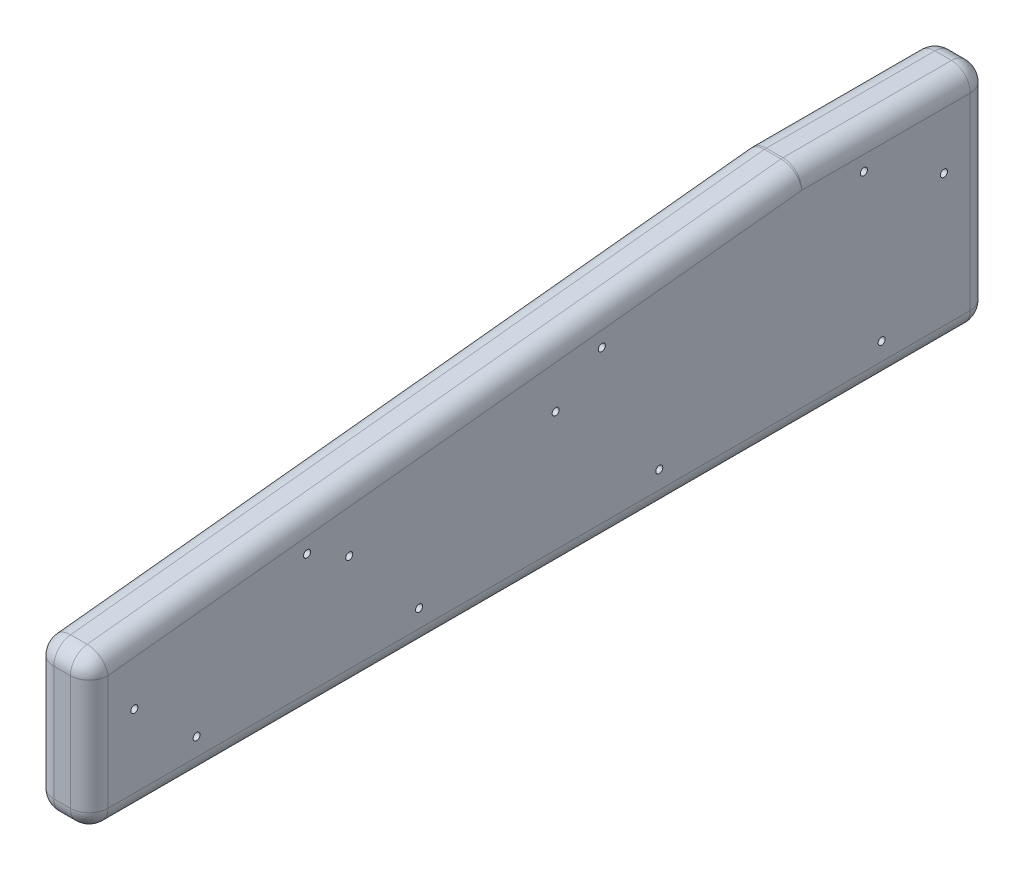
SolidWorks part; units mm, degrees
material "Mahogany"
ref_plane "Front Plane" through (0, 0, 0) normal (0, 0, 1) x (1, 0, 0)
ref_plane "Top Plane" through (0, 0, 0) normal (0, 1, 0) x (1, 0, 0)
ref_plane "Right Plane" through (0, 0, 0) normal (1, 0, 0) x (0, 0, -1)
sketch "Sketch1" plane through (0, 0, 0) normal (1, 0, 0) x (0, 0, -1)
  line L0 (0, 0) -> (0, 84.1309) construction
  line L1 (0, 0) -> (161.7203, 0) construction
  line L2 (-166.9735, -57.6462) -> (123.786, -57.6462)
  line L3 (130.136, -51.2962) -> (130.136, 12.2038)
  line L4 (123.786, 18.5538) -> (66.9711, 18.5538)
  line L5 (66.3027, 18.5185) -> (-167.6419, -6.2448)
  line L6 (-173.3235, -12.5596) -> (-173.3235, -51.2962)
  arc A0 (66.3027, 18.5185) -> (66.9711, 18.5538) centre (66.9711, 12.2038) cw
  arc A1 (123.786, 18.5538) -> (130.136, 12.2038) centre (123.786, 12.2038) cw
  arc A2 (130.136, -51.2962) -> (123.786, -57.6462) centre (123.786, -51.2962) cw
  arc A3 (-166.9735, -57.6462) -> (-173.3235, -51.2962) centre (-166.9735, -51.2962) cw
  arc A4 (-173.3235, -12.5596) -> (-167.6419, -6.2448) centre (-166.9735, -12.5596) cw
  point P11 (66.636, 18.5538)
  point P14 (130.136, 18.5538)
  point P17 (130.136, -57.6462)
  point P20 (-173.3235, -57.6462)
  point P23 (-173.3235, -6.8462)
  dimension "D5" = 6.35
  dimension "D1" = 241.3
  dimension "D2" = 63.5
  dimension "D3" = 76.2
  dimension "D4" = 50.8
extrude "Boss-Extrude1" add sketch "Sketch1" along normal blind 18.288
fillet "Fillet1" radius 6.35 20 edges at (0, 16.6939, -128.2761) (0, -19.5462, -130.136) (0, -55.7864, -128.2761) (0, -57.6462, 21.5938) (0, -55.7864, 171.4636) (0, -31.9279, 173.3235) (0, -8.3123, 171.694) (0, 6.1368, 50.6696) (0, 18.5449, -66.6364) (18.288, 18.5449, -66.6364) (18.288, 18.5538, -95.3785) (18.288, 16.6939, -128.2761) (18.288, -19.5462, -130.136) (18.288, -55.7864, -128.2761) (18.288, -57.6462, 21.5938) (18.288, -55.7864, 171.4636) (18.288, -31.9279, 173.3235) (18.288, -8.3123, 171.694) (0, 18.5538, -95.3785) (18.288, 6.1368, 50.6696)
hole_wizard "3/32 (0.09375) Diameter Hole2" positions "Sketch6" profile "Sketch5" hole size "3/32" standard "ANSI Inch"
sketch "Sketch6" plane through (18.288, 0, 0) normal (1, 0, 0) x (0, 0, -1)
  point P0 (-16.0078, -10.9495)
  point P3 (-85.6189, -18.3179)
sketch "Sketch5" plane through (18.288, -10.9495, 16.0078) normal (0, 1, 0) x (0, 0, -1)
  line L0 (0, 0) -> (0, 10.7154)
  line L1 (0, 10.7154) -> (1.1906, 10)
  line L2 (1.1906, 10) -> (1.1906, 0)
  line L5 (1.1906, 0) -> (0, 0)
  line L10 (0, 10.7154) -> (-1.1906, 10) construction
  line L11 (0, -6.35) -> (0, 107.95) construction
  dimension "Hole Dia." = 2.3812
  dimension "Hole Depth" = 10
  dimension "Drill Angle" = 118
hole_wizard "3/32 (0.09375) Diameter Hole3" positions "Sketch8" profile "Sketch7" hole size "3/32" standard "ANSI Inch"
sketch "Sketch8" plane through (18.288, 0, 0) normal (1, 0, 0) x (0, 0, -1)
  point P0 (114.9252, -6.7962)
  point P3 (-158.0748, -26.7962)
sketch "Sketch7" plane through (18.288, -6.7962, -114.9252) normal (0, 1, 0) x (0, 0, -1)
  line L0 (0, 0) -> (0, 10.6214)
  line L1 (0, 10.6214) -> (1.1906, 9.906)
  line L2 (1.1906, 9.906) -> (1.1906, 0)
  line L5 (1.1906, 0) -> (0, 0)
  line L10 (0, 10.6214) -> (-1.1906, 9.906) construction
  line L11 (0, -6.35) -> (0, 107.95) construction
  dimension "Hole Dia." = 2.3812
  dimension "Hole Depth" = 9.906
  dimension "Drill Angle" = 118
hole_wizard "3/32 (0.09375) Diameter Hole4" positions "Sketch10" profile "Sketch9" hole size "3/32" standard "ANSI Inch"
sketch "Sketch10" plane through (18.288, 0, 0) normal (1, 0, 0) x (0, 0, -1)
  point P0 (93.9245, -45.2962)
  point P3 (18.9245, -45.2962)
  point P6 (-62.0748, -45.2962)
  point P9 (-137.0748, -45.2962)
sketch "Sketch9" plane through (18.288, -45.2962, -93.9245) normal (0, 1, 0) x (0, 0, -1)
  line L0 (0, 0) -> (0, 10.6214)
  line L1 (0, 10.6214) -> (1.1906, 9.906)
  line L2 (1.1906, 9.906) -> (1.1906, 0)
  line L5 (1.1906, 0) -> (0, 0)
  line L10 (0, 10.6214) -> (-1.1906, 9.906) construction
  line L11 (0, -6.35) -> (0, 107.95) construction
  dimension "Hole Dia." = 2.3812
  dimension "Hole Depth" = 9.906
  dimension "Drill Angle" = 118
hole_wizard "3/32 (0.09375) Diameter Hole5" positions "Sketch12" profile "Sketch11" hole size "3/32" standard "ANSI Inch"
sketch "Sketch12" plane through (18.288, 0, 0) normal (1, 0, 0) x (0, 0, -1)
  point P0 (87.9313, 7.1638)
  point P3 (-0.4561, -0.0016)
  point P6 (-99.8304, -10.5205)
sketch "Sketch11" plane through (18.288, 7.1638, -87.9313) normal (0, 1, 0) x (0, 0, -1)
  line L0 (0, 0) -> (0, 10.6214)
  line L1 (0, 10.6214) -> (1.1906, 9.906)
  line L2 (1.1906, 9.906) -> (1.1906, 0)
  line L5 (1.1906, 0) -> (0, 0)
  line L10 (0, 10.6214) -> (-1.1906, 9.906) construction
  line L11 (0, -6.35) -> (0, 107.95) construction
  dimension "Hole Dia." = 2.3812
  dimension "Hole Depth" = 9.906
  dimension "Drill Angle" = 118
